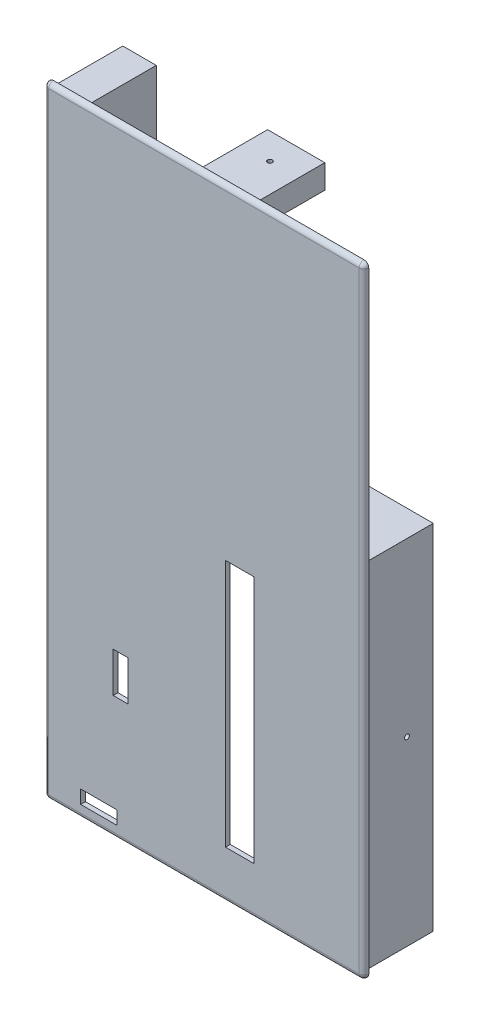
SolidWorks part; units mm, degrees
ref_plane "Piano frontale" through (0, 0, 0) normal (0, 0, 1) x (1, 0, 0)
ref_plane "Piano superiore" through (0, 0, 0) normal (0, 1, 0) x (1, 0, 0)
ref_plane "Piano destro" through (0, 0, 0) normal (1, 0, 0) x (0, 0, -1)
sketch "Schizzo1" plane through (0, 0, 0) normal (0, 0, 1) x (1, 0, 0)
  line L1 (33.5, 65) -> (-33.5, 65)
  line L2 (33.5, 65) -> (33.5, -65)
  line L3 (33.5, -65) -> (-33.5, -65)
  line L4 (-33.5, 65) -> (-33.5, -65)
  line L5 (33.5, 65) -> (-33.5, -65) construction
  line L6 (33.5, -65) -> (-33.5, 65) construction
  point P0 (0, 0)
  dimension "D1" = 67
  dimension "D2" = 130
extrude "Estrusione-Estrusione1" add sketch "Schizzo1" along normal blind 1
fillet "Raccordo1" radius 1 4 edges at (0, 65, 1) (33.5, 0, 1) (0, -65, 1) (-33.5, 0, 1)
fillet "Raccordo2" radius 1 4 edges at (33.2071, -64.7071, 0.7071) (-33.2071, -64.7071, 0.7071) (-33.2071, 64.7071, 0.7071) (33.2071, 64.7071, 0.7071)
sketch "Schizzo2" plane through (0, 0, 1) normal (0, 0, 1) x (1, 0, 0)
  line L0 (32.5, 65) -> (-32.5, 65) construction
  line L1 (4.5, -3) -> (10.5, -3)
  line L2 (4.5, -3) -> (4.5, -55)
  line L3 (4.5, -55) -> (10.5, -55)
  line L4 (10.5, -3) -> (10.5, -55)
  line L5 (4.5, -3) -> (10.5, -55) construction
  line L6 (4.5, -55) -> (10.5, -3) construction
  line L7 (33.5, -64) -> (33.5, 64) construction
  point P0 (7.5, -29)
  dimension "D1" = 68
  dimension "D2" = 23
  dimension "D3" = 52
  dimension "D4" = 6
extrude "Taglio-Estrusione1" cut sketch "Schizzo2" against normal up to next
sketch "Schizzo3" plane through (0, 0, 0) normal (0, 0, -1) x (-1, 0, 0)
  line L0 (-10.5, -55) -> (-10.5, -3) construction
  line L1 (-32.5, -64) -> (-10.5, -64)
  line L2 (-32.5, -64) -> (-32.5, 5)
  line L3 (-10.5, 5.0066) -> (-4.3084, 5.0066)
  line L4 (-10.5, -64) -> (-10.5, 5.0066)
  line L5 (32.5, -65) -> (-32.5, -65) construction
  line L6 (-33.5, -64) -> (-33.5, 64) construction
  line L7 (-4.3084, 5.0066) -> (-4.3084, 9.9639)
  line L8 (-4.3084, 9.9639) -> (-32.5, 9.9639)
  line L9 (-32.5, 9.9639) -> (-32.5, 5)
  line L10 (-32.5, 65) -> (32.5, 65) construction
  line L11 (32.5, 5.0066) -> (25.4808, 5.0066)
  line L12 (32.5, 5.0066) -> (32.5, 64)
  line L13 (32.5, 64) -> (25.4808, 64)
  line L14 (25.4808, 5.0066) -> (25.4808, 64)
  line L15 (33.5, 64) -> (33.5, -64) construction
  line L17 (2.1767, 64) -> (-9.8044, 64)
  line L18 (2.1767, 64) -> (2.1767, 59)
  line L19 (2.1767, 59) -> (-9.8044, 59)
  line L20 (-9.8044, 64) -> (-9.8044, 59)
  dimension "D1" = 1
  dimension "D2" = 1
  dimension "D3" = 1
  dimension "D4" = 1
  dimension "D5" = 1
  dimension "D6" = 5
extrude "Estrusione-Estrusione2" add sketch "Schizzo3" along normal blind 14.5
sketch "Schizzo8" plane through (0, 0, 1) normal (0, 0, 1) x (1, 0, 0)
  line L0 (-32.5, 64) -> (-32.5, -64) construction
  line L1 (-19, -30.8582) -> (-15.9139, -30.8582)
  line L2 (-19, -30.8582) -> (-19, -39.25)
  line L3 (-19, -39.25) -> (-15.9139, -39.25)
  line L4 (-15.9139, -30.8582) -> (-15.9139, -39.25)
  line L5 (-19, -30.8582) -> (-15.9139, -39.25) construction
  line L6 (-19, -39.25) -> (-15.9139, -30.8582) construction
  line L7 (-32.5, -64) -> (32.5, -64) construction
  point P0 (-17.4569, -35.0541)
  dimension "D1" = 24.75
  dimension "D2" = 13.5
extrude "Taglio-Estrusione3" cut sketch "Schizzo8" against normal up to next
sketch "Schizzo10" plane through (0, 0, 1) normal (0, 0, 1) x (1, 0, 0)
  line L0 (-25.8, -59.5964) -> (-18.2367, -59.5964)
  line L1 (-25.8, -59.5964) -> (-25.8, -62.4)
  line L2 (-25.8, -62.4) -> (-18.2367, -62.4)
  line L3 (-18.2367, -59.5964) -> (-18.2367, -62.4)
  line L4 (-25.8, -59.5964) -> (-18.2367, -62.4) construction
  line L5 (-25.8, -62.4) -> (-18.2367, -59.5964) construction
  line L6 (-32.5, -64) -> (32.5, -64) construction
  line L7 (-32.5, 64) -> (-32.5, -64) construction
  point P0 (-22.0184, -60.9982)
  dimension "D1" = 1.6
  dimension "D2" = 6.7
extrude "Taglio-Estrusione4" cut sketch "Schizzo10" against normal up to next
sketch "Schizzo11" plane through (32.5, 0, 0) normal (1, 0, 0) x (0, 0, -1)
  line L0 (0, 9.9639) -> (0, -64) construction
  line L1 (14.5, -64) -> (0, -64) construction
  circle A0 centre (9, -26) radius 0.5
  point P4 (7.25, -64)
  dimension "D1" = 9
  dimension "D2" = 38
extrude "Taglio-Estrusione5" cut sketch "Schizzo11" against normal blind 10
sketch "Schizzo12" plane through (0, 64, 0) normal (0, 1, 0) x (1, 0, 0)
  line L0 (-2.1767, 0) -> (9.8044, 0) construction
  line L1 (3.8138, 9) -> (-2.1767, 9) construction
  line L2 (-2.1767, 14.5) -> (-2.1767, 0) construction
  line L3 (3.8138, 9) -> (9.8044, 9) construction
  line L4 (9.8044, 14.5) -> (9.8044, 0) construction
  circle A0 centre (3.8138, 9) radius 0.5
  dimension "D1" = 9
extrude "Taglio-Estrusione6" cut sketch "Schizzo12" against normal blind 10
sketch "Schizzo13" plane through (-32.5, 0, 0) normal (-1, 0, 0) x (0, 0, 1)
  line L0 (-14.5, 64) -> (0, 64) construction
  line L1 (0, 5.0066) -> (0, 64) construction
  circle A0 centre (-9, 36) radius 0.5
  point P6 (-8.0967, 36.2453)
  dimension "D1" = 28
  dimension "D2" = 9
extrude "Taglio-Estrusione7" cut sketch "Schizzo13" against normal blind 10
sketch "Schizzo14" plane through (0, -64, 0) normal (0, -1, 0) x (1, 0, 0)
  line L0 (32.5, 0) -> (10.5, 0) construction
  line L1 (32.5, -14.5) -> (32.5, 0) construction
  circle A0 centre (20.5, -9) radius 0.5
  dimension "D1" = 9
  dimension "D2" = 12
extrude "Taglio-Estrusione8" cut sketch "Schizzo14" against normal blind 10
